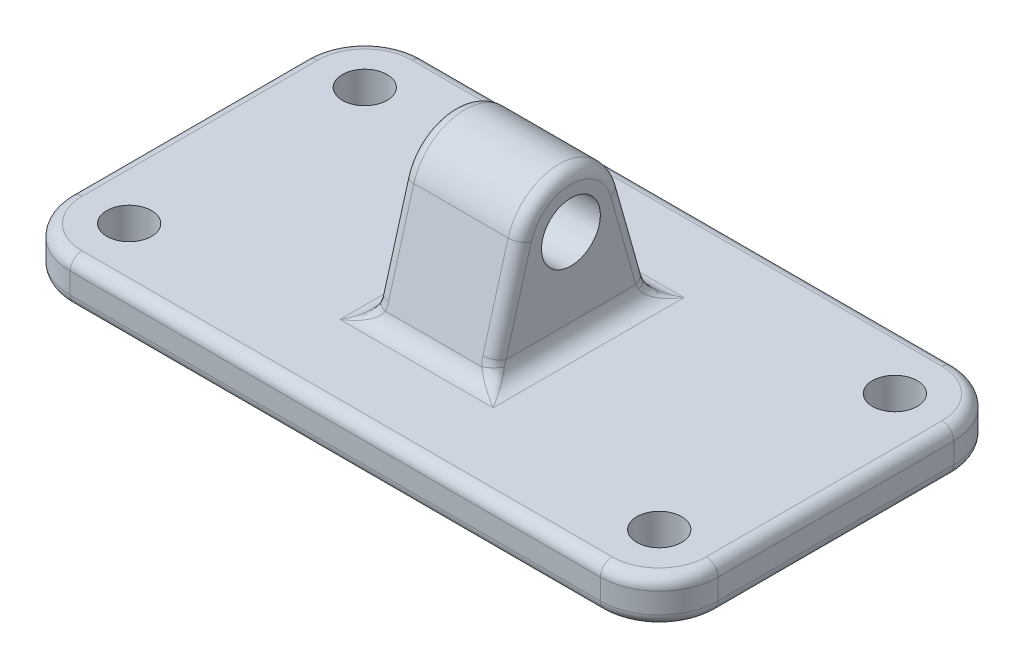
SolidWorks part; units mm, degrees
ref_plane "Front Plane" through (0, 0, 0) normal (0, 0, 1) x (1, 0, 0)
ref_plane "Top Plane" through (0, 0, 0) normal (0, 1, 0) x (1, 0, 0)
ref_plane "Right Plane" through (0, 0, 0) normal (1, 0, 0) x (0, 0, -1)
sketch "Sketch1" plane through (0, 0, 0) normal (0, 1, 0) x (1, 0, 0)
  line L1 (-69.85, 38.1) -> (69.85, 38.1)
  line L2 (-69.85, 38.1) -> (-69.85, -38.1)
  line L3 (-69.85, -38.1) -> (69.85, -38.1)
  line L4 (69.85, 38.1) -> (69.85, -38.1)
  circle A0 centre (-57.15, 25.4) radius 4.826
  circle A1 centre (57.15, 25.4) radius 4.826
  circle A2 centre (57.15, -25.4) radius 4.826
  circle A3 centre (-57.15, -25.4) radius 4.826
  point P0 (0, 0)
  dimension "D2" = 9.652
extrude "Boss-Extrude1" add sketch "Sketch1" along normal mid plane 9.525
sketch "Sketch2" plane through (0, 0, 0) normal (1, 0, 0) x (0, 0, -1)
  line L0 (-19.05, 0) -> (19.05, 0)
  line L1 (0, 0) -> (0, 25.4) construction
  line L4 (-19.05, 0) -> (-10.9998, 28.5063)
  line L5 (19.05, 0) -> (10.9998, 28.5063)
  circle A0 centre (0, 25.4) radius 6.35
  arc A1 (10.9998, 28.5063) -> (-10.9998, 28.5063) centre (0, 25.4) ccw
  circle A2 centre (0, 25.4) radius 6.35
  arc A3 (10.9998, 28.5063) -> (-10.9998, 28.5063) centre (0, 25.4) ccw
  point P4 (0, 0)
  dimension "D1" = 38.1
  dimension "D2" = 25.4
fillet "Fillet1" radius 12.7 4 edges at (69.85, 0, -38.1) (69.85, 0, 38.1) (-69.85, 0, -38.1) (-69.85, 0, 38.1)
fillet "Fillet2" radius 2.54 16 edges at (-66.1303, -4.7625, 34.3803) (-69.85, -4.7625, 0) (-66.1303, -4.7625, -34.3803) (0, -4.7625, -38.1) (66.1303, -4.7625, -34.3803) (69.85, -4.7625, 0) (66.1303, -4.7625, 34.3803) (-66.1303, 4.7625, 34.3803) (-69.85, 4.7625, 0) (-66.1303, 4.7625, -34.3803) (0, 4.7625, -38.1) (66.1303, 4.7625, -34.3803) (69.85, 4.7625, 0) (66.1303, 4.7625, 34.3803) (0, -4.7625, 38.1) (0, 4.7625, 38.1)
extrude "Boss-Extrude3" add sketch "Sketch2" along normal mid plane 25.4 contours L5 A1 L4 L0 A0 region at (0, 14.1269, 0)
fillet "Fillet5" radius 3.81 4 edges at (0, 4.7625, -17.7051) (12.7, 4.7625, 0) (0, 4.7625, 17.7051) (-12.7, 4.7625, 0)
fillet "Fillet6" radius 2.54 14 edges at (-14.211, 5.5343, -18.2891) (-12.736, 8.0498, -16.7767) (-12.7, 18.5394, -13.8145) (-14.211, 5.5343, 18.2891) (-12.736, 8.0498, 16.7767) (-12.7, 18.5394, 13.8145) (14.211, 5.5343, -18.2891) (12.736, 8.0498, -16.7767) (12.7, 18.5394, -13.8145) (14.211, 5.5343, 18.2891) (12.736, 8.0498, 16.7767) (12.7, 18.5394, 13.8145) (-12.7, 36.83, 0) (12.7, 36.83, 0)
